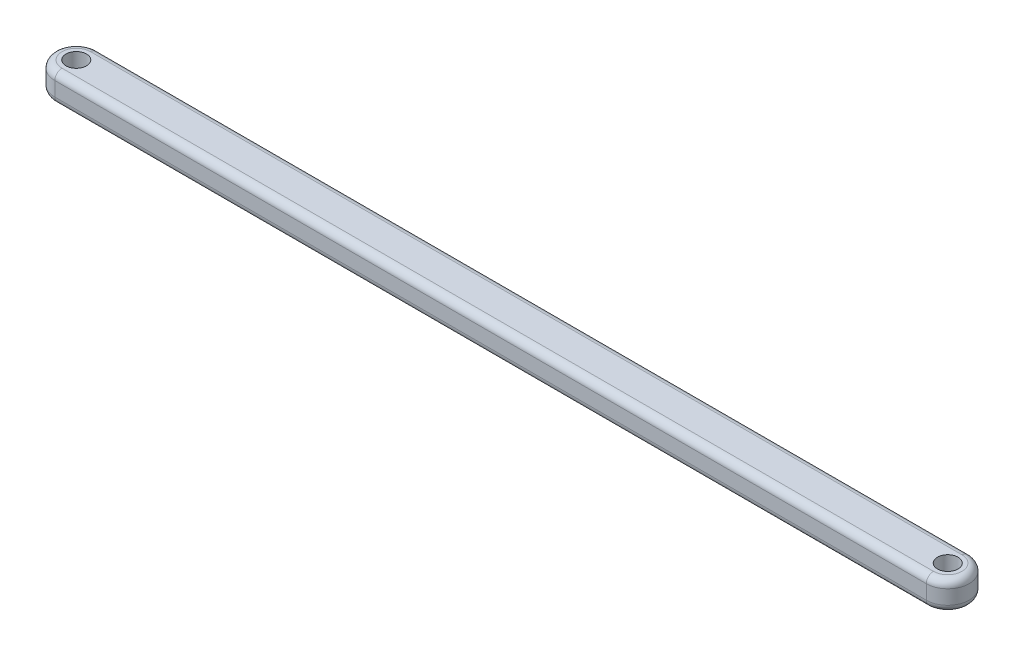
SolidWorks part; units mm, degrees
ref_plane "Front Plane" through (0, 0, 0) normal (0, 0, 1) x (1, 0, 0)
ref_plane "Top Plane" through (0, 0, 0) normal (0, 1, 0) x (1, 0, 0)
ref_plane "Right Plane" through (0, 0, 0) normal (1, 0, 0) x (0, 0, -1)
sketch "Sketch1" plane through (0, 0, 0) normal (0, 1, 0) x (1, 0, 0)
  line L0 (0, 0) -> (193.675, 0) construction
  line L1 (0, 4.7625) -> (193.675, 4.7625)
  line L2 (0, -4.7625) -> (193.675, -4.7625)
  arc A0 (0, 4.7625) -> (0, -4.7625) centre (0, 0) ccw
  arc A1 (193.675, -4.7625) -> (193.675, 4.7625) centre (193.675, 0) ccw
  point P3 (96.8375, 0)
  dimension "D1" = 193.675
  dimension "D2" = 9.525
extrude "Boss-Extrude1" add sketch "Sketch1" along normal mid plane 6.35
sketch "Sketch2" plane through (0, 3.175, 0) normal (0, 1, 0) x (1, 0, 0)
  circle A0 centre (0, 0) radius 2.286
  circle A1 centre (193.675, 0) radius 2.286
  dimension "D1" = 4.572
extrude "Cut-Extrude1" cut sketch "Sketch2" against normal through all
fillet "Fillet1" radius 1.5875 8 edges at (198.4375, -3.175, 0) (96.8375, -3.175, 4.7625) (-4.7625, -3.175, 0) (198.4375, 3.175, 0) (96.8375, 3.175, 4.7625) (-4.7625, 3.175, 0) (96.8375, -3.175, -4.7625) (96.8375, 3.175, -4.7625)
